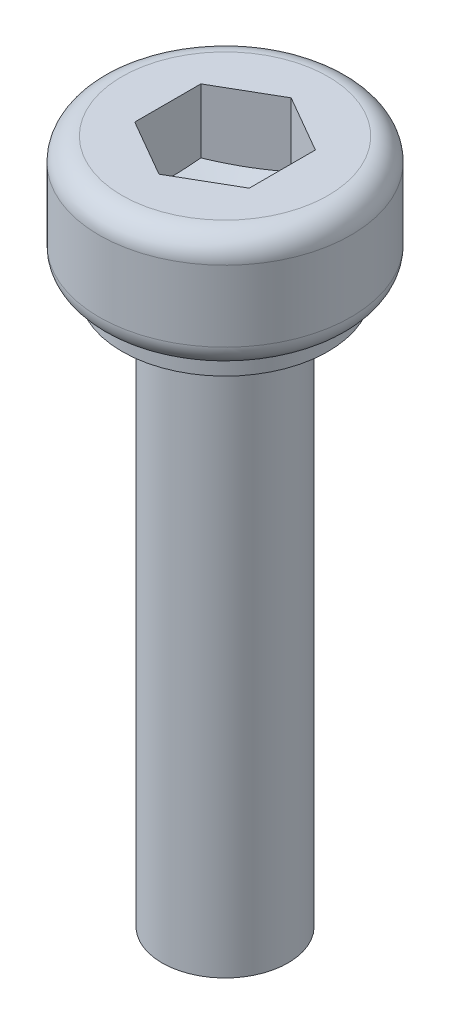
SolidWorks part; units mm, degrees
ref_plane "Front Plane" through (0, 0, 0) normal (0, 0, 1) x (1, 0, 0)
ref_plane "Top Plane" through (0, 0, 0) normal (0, 1, 0) x (1, 0, 0)
ref_plane "Right Plane" through (0, 0, 0) normal (1, 0, 0) x (0, 0, -1)
sketch "Sketch1" plane through (0, 0, 0) normal (0, 0, 1) x (1, 0, 0)
  line L0 (0, 4.0942) -> (0, -5.2249) construction
  line L1 (0, 7.475) -> (2.25, 7.475)
  line L2 (2.75, 6.975) -> (2.75, 5.425)
  line L3 (2.25, 4.525) -> (1.375, 4.525)
  line L4 (1.375, 4.525) -> (1.375, -7.475)
  line L5 (1.375, -7.475) -> (0, -7.475)
  line L6 (0, -7.475) -> (0, 7.475)
  line L7 (2.25, 4.525) -> (2.25, 4.925)
  line L8 (2.75, 4.525) -> (2.25, 4.525) construction
  line L9 (2.75, 5.425) -> (2.75, 4.525) construction
  line L10 (2.75, 7.475) -> (2.75, 6.975) construction
  line L11 (2.25, 7.475) -> (2.75, 7.475) construction
  arc A0 (2.25, 4.925) -> (2.75, 5.425) centre (2.25, 5.425) ccw
  arc A1 (2.25, 7.475) -> (2.75, 6.975) centre (2.25, 6.975) cw
  point P5 (0, 0)
  point P17 (0, 0)
  point P18 (0, 0)
  point P19 (2.25, 2.4541)
  dimension "D5" = 0.5
  dimension "D1" = 12
  dimension "D2" = 1.375
  dimension "D3" = 2.95
  dimension "D4" = 2.75
  dimension "D6" = 0.4
revolve "Revolve1" add sketch "Sketch1" angle 360 about L0
sketch "Sketch2" plane through (0, 7.475, 0) normal (0, 1, 0) x (1, 0, 0)
  line L1 (0, 1.4434) -> (-1.25, 0.7217)
  line L2 (-1.25, 0.7217) -> (-1.25, -0.7217)
  line L3 (-1.25, -0.7217) -> (0, -1.4434)
  line L4 (0, -1.4434) -> (1.25, -0.7217)
  line L5 (1.25, -0.7217) -> (1.25, 0.7217)
  line L6 (1.25, 0.7217) -> (0, 1.4434)
  circle A0 centre (0, 0) radius 1.25 construction
  dimension "D1" = 2.5
extrude "Boss-Extrude1" add sketch "Sketch2" against normal blind 2 separate body
sketch "Sketch3" plane through (0, 0, 0) normal (1, 0, 0) x (0, 0, -1)
  line L0 (0, 5.875) -> (0.4, 5.875)
  line L1 (0.4, 5.875) -> (1.4434, 6.075)
  line L2 (1.4434, 5.475) -> (1.4434, 7.475) construction
  line L3 (1.4434, 6.075) -> (1.4434, 5.475)
  line L4 (1.4434, 5.475) -> (0, 5.475)
  line L5 (-0.7217, 5.475) -> (0.7217, 5.475) construction
  line L6 (0, 5.475) -> (0, 5.875)
  line L7 (-0.7217, 7.475) -> (0.7217, 7.475) construction
  dimension "D1" = 1.6
  dimension "D2" = 1.4
  dimension "D3" = 0.4
revolve "Cut-Revolve1" cut sketch "Sketch3" angle 360 about L6
combine bodies "Combine1" operation type subtract main body 101 bodies to subtract 104
equation "\"Length\"= 12mm"
equation "\"D1@Sketch1\"=\"Length\""
equation "\"ThreadDiam\"= 2.75"
equation "\"D2@Sketch1\"=\"ThreadDiam\"/2"
equation "\"HeadHeight\"=2.95"
equation "\"D3@Sketch1\"=\"HeadHeight\""
equation "\"HeadDiam\"= 5.5"
equation "\"D4@Sketch1\"=\"HeadDiam\"/2"
equation "\"HexSize\"=2.5"
equation "\"D1@Sketch2\"=\"HexSize\""
